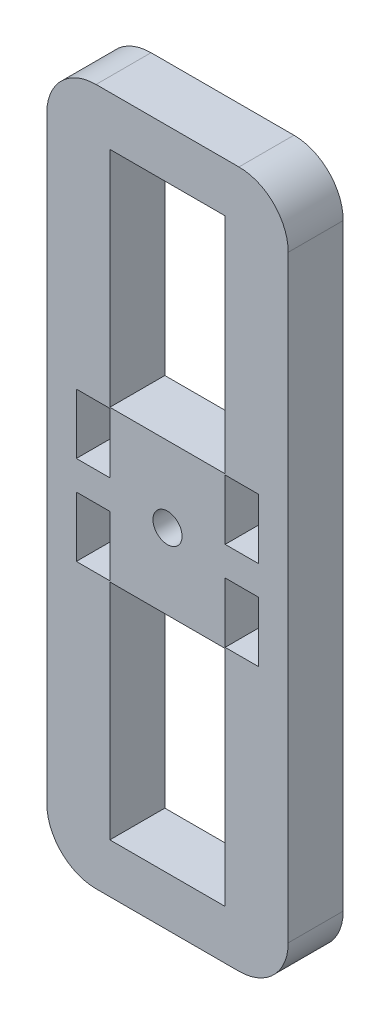
SolidWorks part; units mm, degrees
material "Acrylic (Medium-high impact)"
ref_plane "Front Plane" through (0, 0, 0) normal (0, 0, 1) x (1, 0, 0)
ref_plane "Top Plane" through (0, 0, 0) normal (0, 1, 0) x (1, 0, 0)
ref_plane "Right Plane" through (0, 0, 0) normal (1, 0, 0) x (0, 0, -1)
sketch "Sketch1" plane through (0, 0, 0) normal (0, 0, 1) x (1, 0, 0)
  line L0 (709.8457, 498.2992) -> (721.5457, 498.2992)
  line L1 (721.5457, 498.2992) -> (721.5457, 475.6297)
  line L2 (721.5457, 475.6297) -> (709.8457, 475.6297)
  line L3 (709.8457, 475.6297) -> (709.8457, 498.2992)
  line L4 (715.6957, 432.6102) -> (722.9457, 432.6102)
  line L5 (715.6957, 503.2992) -> (708.4457, 503.2992)
  line L6 (715.6957, 503.2992) -> (722.9457, 503.2992)
  line L7 (715.6957, 460.2797) -> (715.6957, 475.6297) construction
  line L8 (709.8457, 498.2992) -> (703.4457, 498.2992) construction
  line L9 (721.5457, 498.2992) -> (727.9457, 498.2992) construction
  line L10 (709.8457, 475.5297) -> (706.4457, 475.5297)
  line L11 (727.9457, 498.2992) -> (727.9457, 437.6102)
  line L12 (709.8457, 475.5297) -> (709.8457, 469.4297)
  line L13 (709.8457, 469.4297) -> (706.4457, 469.4297)
  line L14 (706.4457, 469.4297) -> (706.4457, 475.5297)
  line L15 (703.4457, 498.2992) -> (703.4457, 437.6102)
  line L16 (721.5457, 475.5297) -> (724.9457, 475.5297)
  line L17 (724.9457, 469.4297) -> (724.9457, 475.5297)
  line L18 (721.5457, 469.4297) -> (724.9457, 469.4297)
  line L19 (721.5457, 475.5297) -> (721.5457, 469.4297)
  line L20 (721.5457, 460.3797) -> (724.9457, 460.3797)
  line L21 (724.9457, 466.4797) -> (724.9457, 460.3797)
  line L22 (715.6957, 432.6102) -> (708.4457, 432.6102)
  line L24 (721.5457, 466.4797) -> (724.9457, 466.4797)
  line L25 (721.5457, 460.3797) -> (721.5457, 466.4797)
  line L26 (709.8457, 460.3797) -> (706.4457, 460.3797)
  line L27 (706.4457, 466.4797) -> (706.4457, 460.3797)
  line L28 (709.8457, 466.4797) -> (706.4457, 466.4797)
  line L29 (709.8457, 460.3797) -> (709.8457, 466.4797)
  line L30 (-282.9616, 469.4297) -> (49717.0384, 469.4297) construction
  line L31 (-282.9616, 466.4797) -> (49717.0384, 466.4797) construction
  line L37 (709.8457, 460.2797) -> (709.8457, 437.6102)
  line L38 (721.5457, 460.2797) -> (709.8457, 460.2797)
  line L39 (721.5457, 437.6102) -> (721.5457, 460.2797)
  line L40 (709.8457, 437.6102) -> (721.5457, 437.6102)
  line L171 (-296.4722, 467.9547) -> (49703.5278, 467.9547) construction
  circle A0 centre (715.6957, 467.9547) radius 1.475
  arc A1 (708.4457, 432.6102) -> (703.4457, 437.6102) centre (708.4457, 437.6102) cw
  arc A2 (708.4457, 503.2992) -> (703.4457, 498.2992) centre (708.4457, 498.2992) ccw
  arc A3 (722.9457, 503.2992) -> (727.9457, 498.2992) centre (722.9457, 498.2992) cw
  arc A4 (722.9457, 432.6102) -> (727.9457, 437.6102) centre (722.9457, 437.6102) ccw
  point P6 (715.6957, 504.6992)
  point P33 (715.6957, 475.6297)
  point P37 (715.6957, 467.9547)
  point P46 (715.6957, 431.2102)
  dimension "D1" = 6.1
  dimension "D4" = 2.95
  dimension "D2" = 3.4
  dimension "D3" = 0.1
  dimension "D5" = 22.6695
  dimension "D6" = 11.7
  dimension "D7" = 3
  dimension "D8" = 5
extrude "Boss-Extrude1" add sketch "Sketch1" along normal blind 5.58 contours L2 L3 L0 L1 L40 L37 L38 L39 A0 region at (712.0707, 433.3583, 0)
